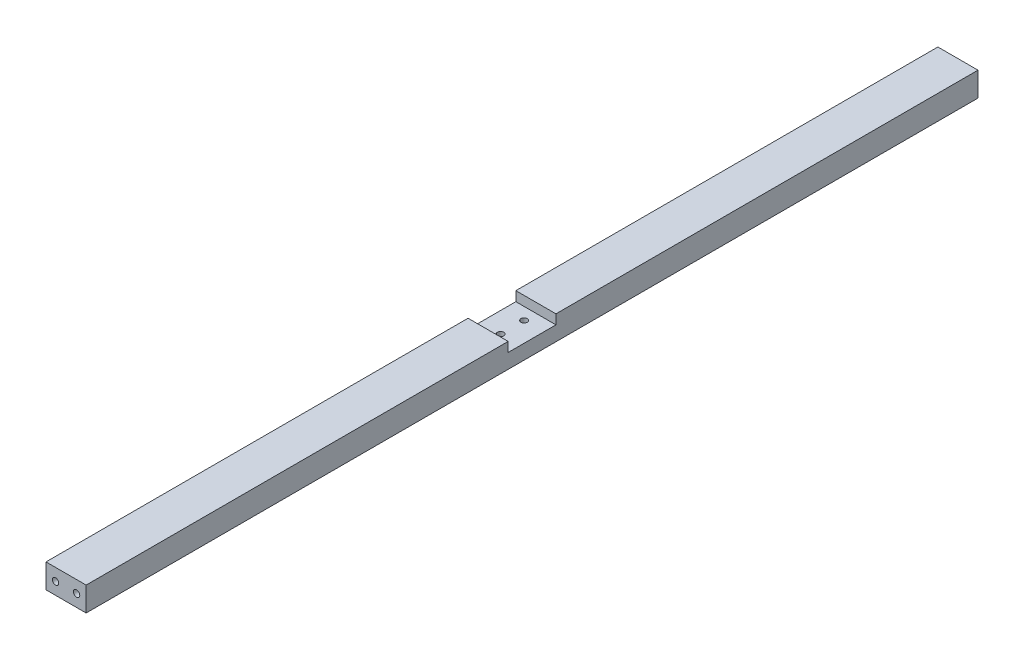
SolidWorks part; units mm, degrees
ref_plane "Front" through (0, 0, 0) normal (0, 0, 1) x (1, 0, 0)
ref_plane "Top" through (0, 0, 0) normal (0, 1, 0) x (1, 0, 0)
ref_plane "Right" through (0, 0, 0) normal (1, 0, 0) x (0, 0, -1)
sketch "Esquisse1" plane through (0, 0, 0) normal (0, 0, 1) x (1, 0, 0)
  line L1 (0, 0) -> (63, 0)
  line L2 (0, 0) -> (0, 38)
  line L3 (0, 38) -> (63, 38)
  line L4 (63, 0) -> (63, 38)
  dimension "D1" = 38
  dimension "D2" = 63
extrude "Boss.-Extru.1" add sketch "Esquisse1" along normal blind 1400
sketch "Esquisse2" plane through (0, 0, 1400) normal (0, 0, 1) x (1, 0, 0)
  line L0 (0, 19) -> (63, 19) construction
  line L1 (0, 38) -> (0, 0) construction
  line L2 (63, 0) -> (63, 38) construction
  line L3 (31.5, 38) -> (31.5, 0) construction
  line L4 (63, 38) -> (0, 38) construction
  line L5 (0, 0) -> (63, 0) construction
  circle A0 centre (15, 19) radius 5
  circle A1 centre (48, 19) radius 5
  dimension "D1" = 10
  dimension "D2" = 15
extrude "Enlèv. mat.-Extru.1" cut sketch "Esquisse2" against normal blind 50
extrude "Enlèv. mat.-Extru.2" cut sketch "Esquisse2<2>" along normal blind 50 from vertex starting at point (0, 0, 0)
sketch "Esquisse2<2>" plane through (0, 0, 1400) normal (0, 0, 1) x (1, 0, 0) same geometry as "Esquisse2"
sketch "Esquisse3" plane through (0, 38, 0) normal (0, 1, 0) x (1, 0, 0)
  line L0 (0, -700) -> (63, -700) construction
  line L1 (0, -1400) -> (0, 0) construction
  line L2 (63, -1400) -> (63, 0) construction
  line L3 (0, -662.5) -> (0, -737.5)
  line L4 (0, -737.5) -> (63, -737.5)
  line L5 (63, -737.5) -> (63, -662.5)
  line L6 (0, -662.5) -> (63, -662.5)
  dimension "D1" = 75
extrude "Enlèv. mat.-Extru.3" cut sketch "Esquisse3" against normal blind 15
sketch "Esquisse4" plane through (0, 23, 0) normal (0, 1, 0) x (1, 0, 0)
  line L0 (32, -737.5) -> (32, -662.5) construction
  line L1 (0, -737.5) -> (63, -737.5) construction
  line L2 (63, -662.5) -> (0, -662.5) construction
  line L3 (32, -700) -> (0, -700) construction
  line L4 (0, -662.5) -> (0, -737.5) construction
  circle A0 centre (32, -718.5) radius 5
  circle A1 centre (32, -681.5) radius 5
  dimension "D1" = 37
  dimension "D2" = 32
  dimension "D3" = 10
extrude "Enlèv. mat.-Extru.4" cut sketch "Esquisse4" against normal through all
